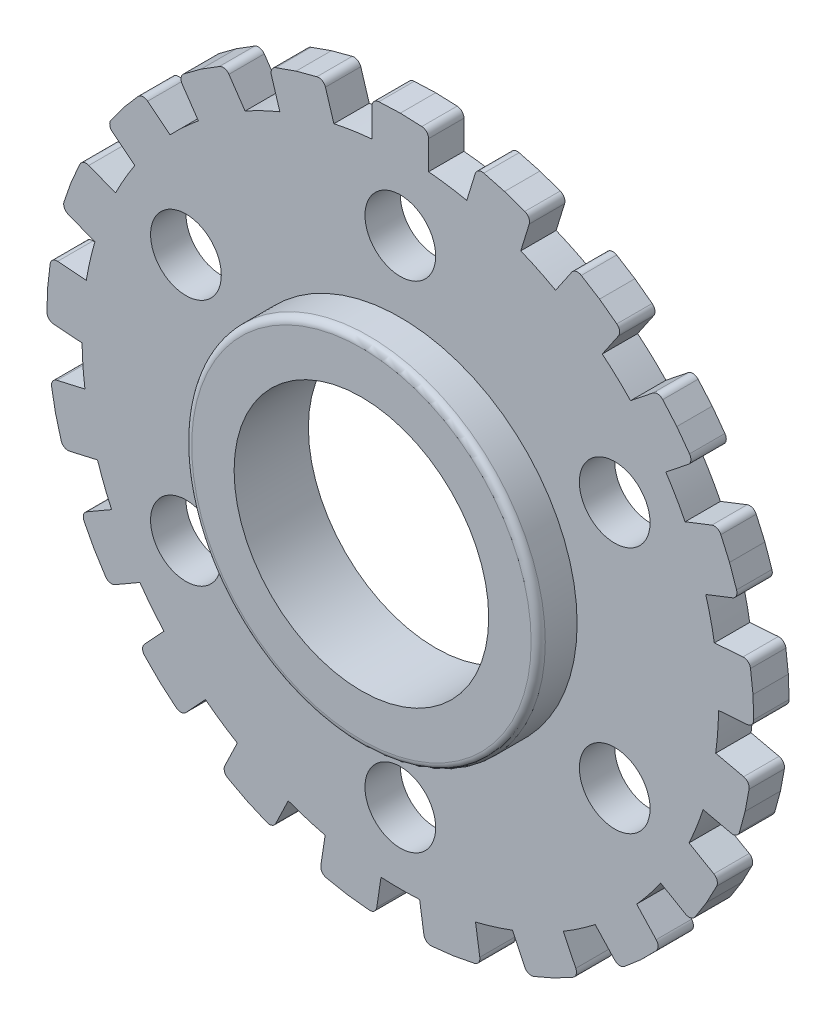
SolidWorks part; units mm, degrees
material "Cast Alloy Steel"
ref_plane "Front Plane" through (0, 0, 0) normal (0, 0, 1) x (1, 0, 0)
ref_plane "Top Plane" through (0, 0, 0) normal (0, 1, 0) x (1, 0, 0)
ref_plane "Right Plane" through (0, 0, 0) normal (1, 0, 0) x (0, 0, -1)
sketch "Sketch1" plane through (0, 0, 0) normal (0, 0, 1) x (1, 0, 0)
  line L0 (0, -45) -> (0, -30) construction
  line L1 (0, 50) -> (-3.0368, 49.8784)
  line L2 (0, 50) -> (3.0368, 49.8784)
  line L3 (-3.9968, 48.8792) -> (-3.9968, 44.8222)
  line L4 (3.9968, 48.8792) -> (3.9968, 44.8222)
  line L5 (14.7378, 47.7786) -> (11.8, 48.5576)
  line L6 (14.7378, 47.7786) -> (17.6038, 46.7674)
  line L7 (10.5882, 47.8857) -> (9.3923, 44.0089)
  line L8 (18.2266, 45.5296) -> (17.0308, 41.6528)
  line L9 (28.166, 41.3119) -> (25.5884, 42.9222)
  line L10 (28.166, 41.3119) -> (30.6066, 39.5008)
  line L11 (24.2323, 42.6374) -> (21.9469, 39.2853)
  line L12 (30.837, 38.1344) -> (28.5515, 34.7823)
  line L13 (39.0916, 31.1745) -> (37.1031, 33.473)
  line L14 (39.0916, 31.1745) -> (40.8899, 28.7244)
  line L15 (35.7234, 33.6005) -> (32.5514, 31.071)
  line L16 (40.7073, 27.3509) -> (37.5353, 24.8213)
  line L17 (46.5437, 18.2671) -> (45.3211, 21.0495)
  line L18 (46.5437, 18.2671) -> (47.54, 15.3958)
  line L19 (44.0402, 21.5781) -> (40.2636, 20.0959)
  line L20 (46.9606, 14.1371) -> (43.184, 12.6549)
  line L21 (49.8602, 3.7365) -> (49.512, 6.7557)
  line L22 (49.8602, 3.7365) -> (49.9659, 0.6991)
  line L23 (48.4439, 7.6384) -> (44.3981, 7.3352)
  line L24 (49.0412, -0.3329) -> (44.9955, -0.6361)
  line L25 (48.7464, -11.126) -> (49.3036, -8.1383)
  line L26 (48.7464, -11.126) -> (47.9521, -14.0597)
  line L27 (48.5431, -6.9801) -> (44.5877, -6.0773)
  line L28 (46.7644, -14.7732) -> (42.809, -13.8705)
  line L29 (43.3013, -25) -> (44.7144, -22.3093)
  line L30 (43.3013, -25) -> (41.6776, -27.5692)
  line L31 (44.3291, -20.9783) -> (40.8155, -18.9497)
  line L32 (40.3323, -27.9009) -> (36.8187, -25.8724)
  line L33 (34.0086, -36.6526) -> (36.1521, -34.4979)
  line L34 (34.0086, -36.6526) -> (31.6998, -38.629)
  line L35 (36.1762, -33.1125) -> (33.4167, -30.1385)
  line L36 (30.3165, -38.5495) -> (27.5569, -35.5755)
  line L37 (21.6942, -45.0484) -> (24.3775, -43.6213)
  line L38 (21.6942, -45.0484) -> (18.9054, -46.2565)
  line L39 (24.8089, -42.3045) -> (23.0486, -38.6492)
  line L40 (17.6069, -45.7728) -> (15.8466, -42.1175)
  line L41 (7.4521, -49.4415) -> (10.4369, -48.8687)
  line L42 (7.4521, -49.4415) -> (4.4311, -49.7739)
  line L43 (11.2372, -47.7376) -> (10.6326, -43.7258)
  line L44 (3.3329, -48.929) -> (2.7282, -44.9172)
  line L45 (-7.4521, -49.4415) -> (-4.4311, -49.7739)
  line L46 (-7.4521, -49.4415) -> (-10.4369, -48.8687)
  line L47 (-3.3329, -48.929) -> (-2.7282, -44.9172)
  line L48 (-11.2372, -47.7376) -> (-10.6326, -43.7258)
  line L49 (-21.6942, -45.0484) -> (-18.9054, -46.2565)
  line L50 (-21.6942, -45.0484) -> (-24.3775, -43.6213)
  line L51 (-17.6069, -45.7728) -> (-15.8466, -42.1175)
  line L52 (-24.8089, -42.3045) -> (-23.0486, -38.6492)
  line L53 (-34.0086, -36.6526) -> (-31.6998, -38.629)
  line L54 (-34.0086, -36.6526) -> (-36.1521, -34.4979)
  line L55 (-30.3165, -38.5495) -> (-27.5569, -35.5755)
  line L56 (-36.1762, -33.1125) -> (-33.4167, -30.1385)
  line L57 (-43.3013, -25) -> (-41.6776, -27.5692)
  line L58 (-43.3013, -25) -> (-44.7144, -22.3093)
  line L59 (-40.3323, -27.9009) -> (-36.8187, -25.8724)
  line L60 (-44.3291, -20.9783) -> (-40.8155, -18.9497)
  line L61 (-48.7464, -11.126) -> (-47.9521, -14.0597)
  line L62 (-48.7464, -11.126) -> (-49.3036, -8.1383)
  line L63 (-46.7644, -14.7732) -> (-42.809, -13.8705)
  line L64 (-48.5431, -6.9801) -> (-44.5877, -6.0773)
  line L65 (-49.8602, 3.7365) -> (-49.9659, 0.6991)
  line L66 (-49.8602, 3.7365) -> (-49.512, 6.7557)
  line L67 (-49.0412, -0.3329) -> (-44.9955, -0.6361)
  line L68 (-48.4439, 7.6384) -> (-44.3981, 7.3352)
  line L69 (-46.5437, 18.2671) -> (-47.54, 15.3958)
  line L70 (-46.5437, 18.2671) -> (-45.3211, 21.0495)
  line L71 (-46.9606, 14.1371) -> (-43.184, 12.6549)
  line L72 (-44.0402, 21.5781) -> (-40.2636, 20.0959)
  line L73 (-39.0916, 31.1745) -> (-40.8899, 28.7244)
  line L74 (-39.0916, 31.1745) -> (-37.1031, 33.473)
  line L75 (-40.7073, 27.3509) -> (-37.5353, 24.8213)
  line L76 (-35.7234, 33.6005) -> (-32.5514, 31.071)
  line L77 (-28.166, 41.3119) -> (-30.6066, 39.5008)
  line L78 (-28.166, 41.3119) -> (-25.5884, 42.9222)
  line L79 (-30.837, 38.1344) -> (-28.5515, 34.7823)
  line L80 (-24.2323, 42.6374) -> (-21.9469, 39.2853)
  line L81 (-14.7378, 47.7786) -> (-17.6038, 46.7674)
  line L82 (-14.7378, 47.7786) -> (-11.8, 48.5576)
  line L83 (-18.2266, 45.5296) -> (-17.0308, 41.6528)
  line L84 (-10.5882, 47.8857) -> (-9.3923, 44.0089)
  line L85 (0, 18) -> (0, 30) construction
  line L86 (0, 40) -> (0, 45.5552) construction
  circle A0 centre (0, 0) radius 18
  circle A1 centre (0, 0) radius 25
  arc A2 (-37.5353, 24.8213) -> (-40.2636, 20.0959) centre (0, 0) ccw
  circle A4 centre (0, 35) radius 5
  arc A5 (3.0368, 49.8784) -> (3.9968, 48.8792) centre (2.9968, 48.8792) cw
  arc A6 (-3.0368, 49.8784) -> (-3.9968, 48.8792) centre (-2.9968, 48.8792) ccw
  arc A7 (17.6038, 46.7674) -> (18.2266, 45.5296) centre (17.2711, 45.8243) cw
  arc A8 (11.8, 48.5576) -> (10.5882, 47.8857) centre (11.5437, 47.591) ccw
  arc A9 (30.6066, 39.5008) -> (30.837, 38.1344) centre (30.0107, 38.6978) cw
  arc A10 (25.5884, 42.9222) -> (24.2323, 42.6374) centre (25.0586, 42.0741) ccw
  arc A11 (40.8899, 28.7244) -> (40.7073, 27.3509) centre (40.0838, 28.1327) cw
  arc A12 (37.1031, 33.473) -> (35.7234, 33.6005) centre (36.3468, 32.8187) ccw
  arc A13 (47.54, 15.3958) -> (46.9606, 14.1371) centre (46.5952, 15.0679) cw
  arc A14 (45.3211, 21.0495) -> (44.0402, 21.5781) centre (44.4055, 20.6472) ccw
  arc A15 (49.9659, 0.6991) -> (49.0412, -0.3329) centre (48.9665, 0.6643) cw
  arc A16 (49.512, 6.7557) -> (48.4439, 7.6384) centre (48.5186, 6.6412) ccw
  arc A17 (47.9521, -14.0597) -> (46.7644, -14.7732) centre (46.9869, -13.7983) cw
  arc A18 (49.3036, -8.1383) -> (48.5431, -6.9801) centre (48.3206, -7.955) ccw
  arc A19 (41.6776, -27.5692) -> (40.3323, -27.9009) centre (40.8323, -27.0349) cw
  arc A20 (44.7144, -22.3093) -> (44.3291, -20.9783) centre (43.8291, -21.8443) ccw
  arc A21 (31.6998, -38.629) -> (30.3165, -38.5495) centre (31.0495, -37.8694) cw
  arc A22 (36.1521, -34.4979) -> (36.1762, -33.1125) centre (35.4431, -33.7927) ccw
  arc A23 (18.9054, -46.2565) -> (17.6069, -45.7728) centre (18.5079, -45.3389) cw
  arc A24 (24.3775, -43.6213) -> (24.8089, -42.3045) centre (23.9079, -42.7384) ccw
  arc A25 (4.4311, -49.7739) -> (3.3329, -48.929) centre (4.3217, -48.7799) cw
  arc A26 (10.4369, -48.8687) -> (11.2372, -47.7376) centre (10.2484, -47.8866) ccw
  arc A27 (-10.4369, -48.8687) -> (-11.2372, -47.7376) centre (-10.2484, -47.8866) cw
  arc A28 (-4.4311, -49.7739) -> (-3.3329, -48.929) centre (-4.3217, -48.7799) ccw
  arc A29 (-24.3775, -43.6213) -> (-24.8089, -42.3045) centre (-23.9079, -42.7384) cw
  arc A30 (-18.9054, -46.2565) -> (-17.6069, -45.7728) centre (-18.5079, -45.3389) ccw
  arc A31 (-36.1521, -34.4979) -> (-36.1762, -33.1125) centre (-35.4431, -33.7927) cw
  arc A32 (-31.6998, -38.629) -> (-30.3165, -38.5495) centre (-31.0495, -37.8694) ccw
  arc A33 (-44.7144, -22.3093) -> (-44.3291, -20.9783) centre (-43.8291, -21.8443) cw
  arc A34 (-41.6776, -27.5692) -> (-40.3323, -27.9009) centre (-40.8323, -27.0349) ccw
  arc A35 (-49.3036, -8.1383) -> (-48.5431, -6.9801) centre (-48.3206, -7.955) cw
  arc A36 (-47.9521, -14.0597) -> (-46.7644, -14.7732) centre (-46.9869, -13.7983) ccw
  arc A37 (-49.512, 6.7557) -> (-48.4439, 7.6384) centre (-48.5186, 6.6412) cw
  arc A38 (-49.9659, 0.6991) -> (-49.0412, -0.3329) centre (-48.9665, 0.6643) ccw
  arc A39 (-45.3211, 21.0495) -> (-44.0402, 21.5781) centre (-44.4055, 20.6472) cw
  arc A40 (-47.54, 15.3958) -> (-46.9606, 14.1371) centre (-46.5952, 15.0679) ccw
  arc A41 (-37.1031, 33.473) -> (-35.7234, 33.6005) centre (-36.3468, 32.8187) cw
  arc A42 (-40.8899, 28.7244) -> (-40.7073, 27.3509) centre (-40.0838, 28.1327) ccw
  arc A43 (-25.5884, 42.9222) -> (-24.2323, 42.6374) centre (-25.0586, 42.0741) cw
  arc A44 (-30.6066, 39.5008) -> (-30.837, 38.1344) centre (-30.0107, 38.6978) ccw
  arc A45 (-11.8, 48.5576) -> (-10.5882, 47.8857) centre (-11.5437, 47.591) cw
  arc A46 (-17.6038, 46.7674) -> (-18.2266, 45.5296) centre (-17.2711, 45.8243) ccw
  circle A47 centre (30.3109, 17.5) radius 5
  circle A48 centre (30.3109, -17.5) radius 5
  circle A49 centre (0, -35) radius 5
  circle A50 centre (-30.3109, -17.5) radius 5
  circle A51 centre (-30.3109, 17.5) radius 5
  arc A52 (-28.5515, 34.7823) -> (-32.5514, 31.071) centre (0, 0) ccw
  arc A53 (-17.0308, 41.6528) -> (-21.9469, 39.2853) centre (0, 0) ccw
  arc A54 (-3.9968, 44.8222) -> (-9.3923, 44.0089) centre (0, 0) ccw
  arc A55 (9.3923, 44.0089) -> (3.9968, 44.8222) centre (0, 0) ccw
  arc A56 (21.9469, 39.2853) -> (17.0308, 41.6528) centre (0, 0) ccw
  arc A57 (32.5514, 31.071) -> (28.5515, 34.7823) centre (0, 0) ccw
  arc A58 (40.2636, 20.0959) -> (37.5353, 24.8213) centre (0, 0) ccw
  arc A59 (44.3981, 7.3352) -> (43.184, 12.6549) centre (0, 0) ccw
  arc A60 (44.5877, -6.0773) -> (44.9955, -0.6361) centre (0, 0) ccw
  arc A61 (40.8155, -18.9497) -> (42.809, -13.8705) centre (0, 0) ccw
  arc A62 (33.4167, -30.1385) -> (36.8187, -25.8724) centre (0, 0) ccw
  arc A63 (23.0486, -38.6492) -> (27.5569, -35.5755) centre (0, 0) ccw
  arc A64 (10.6326, -43.7258) -> (15.8466, -42.1175) centre (0, 0) ccw
  arc A65 (-2.7282, -44.9172) -> (2.7282, -44.9172) centre (0, 0) ccw
  arc A66 (-15.8466, -42.1175) -> (-10.6326, -43.7258) centre (0, 0) ccw
  arc A67 (-27.5569, -35.5755) -> (-23.0486, -38.6492) centre (0, 0) ccw
  arc A68 (-36.8187, -25.8724) -> (-33.4167, -30.1385) centre (0, 0) ccw
  arc A69 (-42.809, -13.8705) -> (-40.8155, -18.9497) centre (0, 0) ccw
  arc A70 (-44.9955, -0.6361) -> (-44.5877, -6.0773) centre (0, 0) ccw
  arc A71 (-43.184, 12.6549) -> (-44.3981, 7.3352) centre (0, 0) ccw
  point P5 (0, 0)
  point P17 (3.9968, 49.84)
  point P20 (-3.9968, 49.84)
  point P22 (-3.9968, 44.8222)
  point P23 (3.9968, 44.8222)
  point P34 (9.3923, 44.0089)
  point P35 (17.0308, 41.6528)
  point P45 (21.9469, 39.2853)
  point P46 (28.5515, 34.7823)
  point P56 (32.5514, 31.071)
  point P57 (37.5353, 24.8213)
  point P67 (40.2636, 20.0959)
  point P68 (43.184, 12.6549)
  point P78 (44.3981, 7.3352)
  point P79 (44.9955, -0.6361)
  point P89 (44.5877, -6.0773)
  point P90 (42.809, -13.8705)
  point P100 (40.8155, -18.9497)
  point P101 (36.8187, -25.8724)
  point P111 (33.4167, -30.1385)
  point P112 (27.5569, -35.5755)
  point P122 (23.0486, -38.6492)
  point P123 (15.8466, -42.1175)
  point P133 (10.6326, -43.7258)
  point P134 (2.7282, -44.9172)
  point P144 (-2.7282, -44.9172)
  point P145 (-10.6326, -43.7258)
  point P155 (-15.8466, -42.1175)
  point P156 (-23.0486, -38.6492)
  point P166 (-27.5569, -35.5755)
  point P167 (-33.4167, -30.1385)
  point P177 (-36.8187, -25.8724)
  point P178 (-40.8155, -18.9497)
  point P188 (-42.809, -13.8705)
  point P189 (-44.5877, -6.0773)
  point P199 (-44.9955, -0.6361)
  point P200 (-44.3981, 7.3352)
  point P210 (-43.184, 12.6549)
  point P211 (-40.2636, 20.0959)
  point P221 (-37.5353, 24.8213)
  point P222 (-32.5514, 31.071)
  point P232 (-28.5515, 34.7823)
  point P233 (-21.9469, 39.2853)
  point P243 (-17.0308, 41.6528)
  point P244 (-9.3923, 44.0089)
  point P245 (0, 0)
  point P255 (0, 0)
  dimension "D1" = 1
  dimension "D3" = 35
  dimension "D2" = 21
  dimension "D4" = 6
extrude "Boss-Extrude4" add sketch "Sketch1" along normal mid plane 5 contours L71 A71 L68 A37 L66 L65 A38 L67 A70 L64 A35 L62 L61 A36 L63 A69 L60 A33 L58 L57 A34 L59 A68 L56 A31 L54 L53 A32 L55 A67 L52 A29 L50 L49 A30 L51 A66 L48 A27 L46 L45 A28 L47 A65 A49 A1 A4 | A1 L0 A0 | L0 A1 A0 region at (1.4619, 48.5282, 0) region at (-24.2929, 0, 0)
extrude "Boss-Extrude6" add sketch "Sketch1<9>" along normal blind 8 contours A1
sketch "Sketch1<9>" plane through (0, 0, 0) normal (0, 0, 1) x (1, 0, 0) same geometry as "Sketch1"
extrude "Cut-Extrude5" cut sketch "Sketch1<10>" against normal through all both and the other way through all contours A0
sketch "Sketch1<10>" plane through (0, 0, 0) normal (0, 0, 1) x (1, 0, 0) same geometry as "Sketch1"
fillet "Fillet1" radius 1 1 edges at (25, 0, 8)
